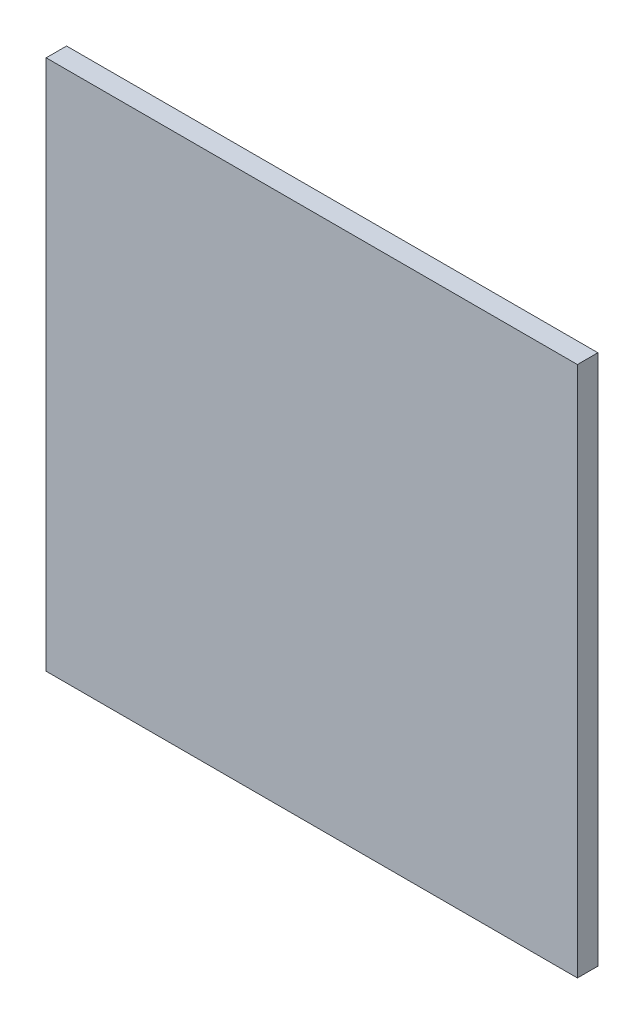
SolidWorks part; units mm, degrees
ref_plane "Plan de face" through (0, 0, 0) normal (0, 0, 1) x (1, 0, 0)
ref_plane "Plan de dessus" through (0, 0, 0) normal (0, 1, 0) x (1, 0, 0)
ref_plane "Plan de droite" through (0, 0, 0) normal (1, 0, 0) x (0, 0, -1)
sketch "Esquisse1" plane through (0, 0, 0) normal (0, 0, 1) x (1, 0, 0)
  line L1 (-260, 260) -> (260, 260)
  line L2 (-260, 260) -> (-260, -260)
  line L3 (-260, -260) -> (260, -260)
  line L4 (260, 260) -> (260, -260)
  line L5 (-260, 260) -> (260, -260) construction
  line L6 (-260, -260) -> (260, 260) construction
  point P0 (0, 0)
  dimension "D1" = 520
  dimension "D2" = 520
extrude "Boss.-Extru.1" add sketch "Esquisse1" along normal blind 20
